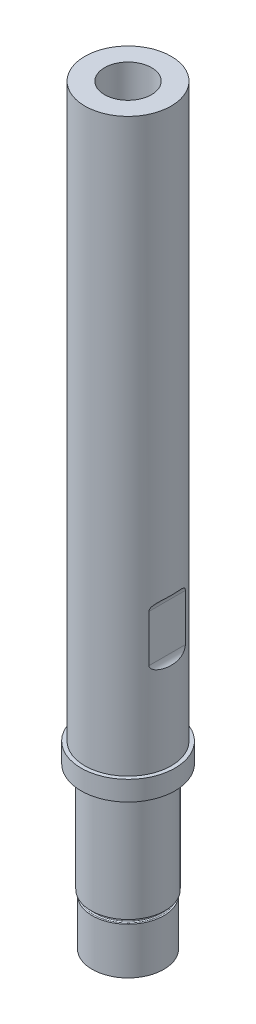
SolidWorks part; units mm, degrees
material "AISI 304"
ref_plane "Front Plane" through (0, 0, 0) normal (0, 0, 1) x (1, 0, 0)
ref_plane "Top Plane" through (0, 0, 0) normal (0, 1, 0) x (1, 0, 0)
ref_plane "Right Plane" through (0, 0, 0) normal (1, 0, 0) x (0, 0, -1)
sketch "Sketch1" plane through (0, 0, 0) normal (0, 1, 0) x (1, 0, 0)
  circle A0 centre (0, 0) radius 9.525
  circle A1 centre (0, 0) radius 22.5
  dimension "D1" = 45
  dimension "D2" = 19.05
extrude "Boss-Extrude1" add sketch "Sketch1" along normal blind 95
sketch "Sketch2" plane through (0, 0, 0) normal (0, -1, 0) x (1, 0, 0)
  circle A0 centre (0, 0) radius 15
  dimension "D1" = 30
extrude "Cut-Extrude1" cut sketch "Sketch2" against normal blind 50 flip side to cut
sketch "Sketch4" plane through (0, 95, 0) normal (0, 1, 0) x (1, 0, 0)
  circle A0 centre (0, 0) radius 17.5
  dimension "D1" = 35
extrude "Cut-Extrude2" cut sketch "Sketch4" against normal blind 37 flip side to cut
sketch "Sketch11" plane through (0, 0, 0) normal (0, -1, 0) x (1, 0, 0)
  circle A0 centre (0, 0) radius 14.513
  dimension "D1" = 29.026
extrude "Cut-Extrude3" cut sketch "Sketch11" against normal blind 5.88 flip side to cut
sketch "Sketch12" plane through (0, 95, 0) normal (0, 1, 0) x (1, 0, 0)
  circle A0 centre (0, 0) radius 9.525 construction
  circle A1 centre (0, 0) radius 17.5
  circle A2 centre (0, 0) radius 17.5
  circle A3 centre (0, 0) radius 9.525
  dimension "D1" = 0
extrude "Boss-Extrude2" add sketch "Sketch12" along normal blind 203.2
sketch "Sketch13" plane through (0, 0, 0) normal (0, -1, 0) x (1, 0, 0)
  circle A0 centre (0, 0) radius 9.525
  circle A1 centre (0, 0) radius 15
  circle A2 centre (0, 0) radius 14.513
  circle A3 centre (0, 0) radius 14.513 construction
  circle A4 centre (0, 0) radius 9.525 construction
  circle M2 centre (0, 0) radius 14.513
  dimension "D2" = 30
  dimension "D3" = 0
extrude "Boss-Extrude3" add sketch "Sketch13" along normal blind 15 contours A1 M2 region at (-14.1025, 0, 0)
sketch "Sketch15" plane through (0, 50, 0) normal (0, -1, 0) x (1, 0, 0)
  circle A0 centre (0, 0) radius 19.05
  dimension "D1" = 38.1
extrude "Cut-Extrude5" cut sketch "Sketch15" against normal through all flip side to cut
sketch "Sketch16" plane through (0, 5.88, 0) normal (0, -1, 0) x (1, 0, 0)
  circle A0 centre (0, 0) radius 13.5
  dimension "D1" = 27
extrude "Cut-Extrude6" cut sketch "Sketch16" along normal blind 2 flip side to cut
fillet "Fillet2" radius 0.3969 2 edges at (0, 5.88, -13.5) (0, 3.88, -13.5)
sketch "Sketch17" plane through (0, 298.2, 0) normal (0, 1, 0) x (1, 0, 0)
  circle A1 centre (0, 0) radius 17.5
  circle A2 centre (0, 0) radius 17.5
  dimension "D1" = 0
extrude "Cut-Extrude7" cut sketch "Sketch17" against normal offset from surface (8.4 mm away) 304.8 up to face at (0, -15, -14.513)
sketch "Sketch20" plane through (0, 0, 0) normal (0, 0, 1) x (1, 0, 0)
  line L1 (-19.05, 118.325) -> (-15.875, 118.325)
  line L2 (-19.05, 118.325) -> (-19.05, 92.925)
  line L3 (-19.05, 92.925) -> (-15.875, 92.925)
  line L4 (-15.875, 118.325) -> (-15.875, 92.925)
  line L5 (15.875, 118.325) -> (19.05, 118.325)
  line L6 (15.875, 118.325) -> (15.875, 92.925)
  line L7 (15.875, 92.925) -> (19.05, 92.925)
  line L8 (19.05, 118.325) -> (19.05, 92.925)
  line L9 (0, 289.8) -> (0, -15) construction
  line L10 (19.05, 58) -> (-19.05, 58) construction
  line L11 (-19.05, 58) -> (-19.05, 50) construction
  line L12 (19.05, 50) -> (19.05, 58) construction
  dimension "D2" = 15.875
  dimension "D1" = 15.875
  dimension "D3" = 34.925
  dimension "D4" = 25.4
extrude "Cut-Extrude8" cut sketch "Sketch20" against normal through all both and the other way through all
fillet "Fillet3" radius 3.175 4 edges at (-15.875, 92.925, 0) (-15.875, 118.325, 0) (15.875, 92.925, 0) (15.875, 118.325, 0)
equation "\"D1@Sketch20\"=\"D2@Sketch20\""
